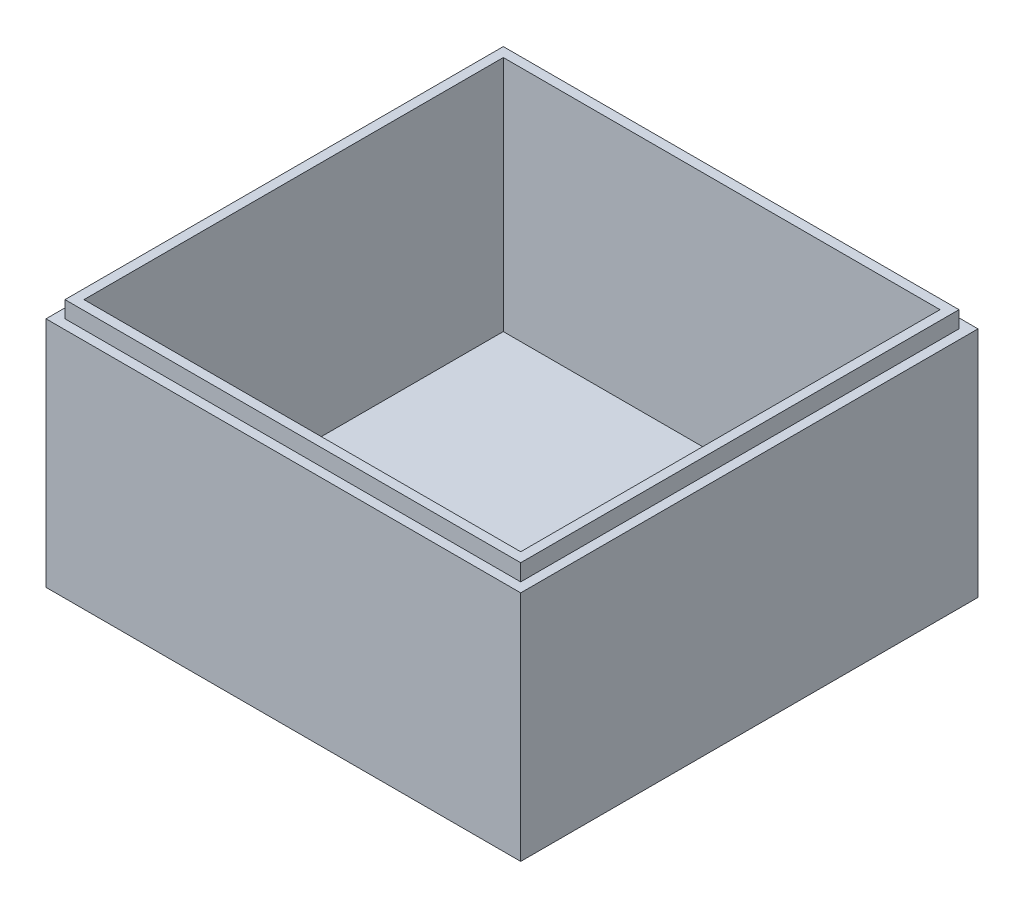
SolidWorks part; units mm, degrees
ref_plane "Front Plane" through (0, 0, 0) normal (0, 0, 1) x (1, 0, 0)
ref_plane "Top Plane" through (0, 0, 0) normal (0, 1, 0) x (1, 0, 0)
ref_plane "Right Plane" through (0, 0, 0) normal (1, 0, 0) x (0, 0, -1)
sketch "BatteryAndOuterWalls" plane through (0, 0, 0) normal (0, 1, 0) x (1, 0, 0)
  line L0 (30, -28.9) -> (30, 28.9)
  line L1 (27.6, -26.5) -> (-27.6, -26.5)
  line L2 (27.6, -26.5) -> (27.6, 26.5)
  line L3 (27.6, 26.5) -> (-27.6, 26.5)
  line L4 (-27.6, -26.5) -> (-27.6, 26.5)
  line L5 (27.6, -26.5) -> (-27.6, 26.5) construction
  line L6 (27.6, 26.5) -> (-27.6, -26.5) construction
  line L7 (30, 28.9) -> (-30, 28.9)
  line L8 (-30, -28.9) -> (-30, 28.9)
  line L9 (30, -28.9) -> (-30, -28.9)
  point P0 (0, 0)
  dimension "D1" = 55.2
  dimension "D2" = 53
  dimension "D4" = 60
  dimension "D5" = 57.8
  dimension "D3" = 2.4
extrude "Walls" add sketch "BatteryAndOuterWalls" along normal blind 30
sketch "SinkRim" plane through (0, 30, 0) normal (0, 1, 0) x (1, 0, 0)
  line L0 (-28.8, 27.7) -> (-28.8, -27.7)
  line L5 (-27.6, 26.5) -> (27.6, 26.5)
  line L6 (-27.6, 26.5) -> (-27.6, -26.5)
  line L7 (-27.6, -26.5) -> (27.6, -26.5)
  line L8 (27.6, 26.5) -> (27.6, -26.5)
  line L9 (-28.8, -27.7) -> (28.8, -27.7)
  line L10 (28.8, 27.7) -> (28.8, -27.7)
  line L11 (-28.8, 27.7) -> (28.8, 27.7)
  line L12 (-30, 28.9) -> (30, 28.9)
  line L13 (30, 28.9) -> (30, -28.9)
  line L14 (-30, -28.9) -> (30, -28.9)
  line L15 (-30, 28.9) -> (-30, -28.9)
  line M5 (-30, -28.9) -> (30, -28.9)
  line M6 (30, -28.9) -> (30, 28.9)
  line M7 (30, 28.9) -> (-30, 28.9)
  line M8 (-30, 28.9) -> (-30, -28.9)
  dimension "D1" = 1.2
  dimension "D2" = 1.2
sketch "Sketch2" plane through (0, 0, 0) normal (0, -1, 0) x (1, 0, 0)
  line L0 (-30, 28.9) -> (30, 28.9) construction
  line L5 (-30, 28.9) -> (30, 28.9)
  line L6 (-30, 28.9) -> (-30, -28.9)
  line L7 (-30, -28.9) -> (30, -28.9)
  line L8 (30, 28.9) -> (30, -28.9)
  line L9 (-30, -28.9) -> (-30, 28.9) construction
extrude "Bottom" add sketch "Sketch2" along normal blind 1.5
extrude "Top-Cut" cut sketch "SinkRim" against normal blind 2.1 contours L0 L11 L10 L9 M8 M5 M6 M7 region at (0, 30, -28.0669)
sketch "FrontRail" plane through (30, 0, 0) normal (1, 0, 0) x (0, 0, -1)
  line L0 (-28.9, 27.9) -> (-28.9, -1.5) construction
  line L1 (-26.5, 30) -> (26.5, 30)
  line L2 (-26.5, 30) -> (-26.5, 0)
  line L3 (-26.5, 0) -> (26.5, 0)
  line L4 (26.5, 30) -> (26.5, 0)
  line L5 (28.9, -1.5) -> (-28.9, -1.5) construction
  line L6 (28.9, 27.9) -> (28.9, -1.5) construction
  line L7 (27.7, 30) -> (-27.7, 30) construction
  line L8 (-26.5, 13) -> (-26.5, 14)
  line L10 (-26.5, 15) -> (-26.5, 14)
  line L29 (-26.5, 13) -> (-26.5, 14)
  line L30 (-26.5, 14) -> (-26.5, 13)
  line L32 (-26.5, 16.5) -> (26.5, 16.5)
  line L33 (-26.5, 16.5) -> (-26.5, 15)
  line L34 (-26.5, 15) -> (26.5, 15)
  line L35 (26.5, 16.5) -> (26.5, 15)
  line L36 (-22.5, 16.5) -> (22.5, 16.5)
  line L37 (-22.5, 16.5) -> (-22.5, 15)
  line L38 (-22.5, 15) -> (22.5, 15)
  line L41 (-22.5, 15) -> (-26.5, 15)
  line L42 (-22.5, 15) -> (-22.5, 14.95)
  line L43 (-23.45, 14) -> (-26.5, 14)
  line L44 (-26.5, 15) -> (-26.5, 14)
  arc A0 (-22.5, 14.95) -> (-23.45, 14) centre (-23.45, 14.95) cw
  point P26 (0, 0)
  point P27 (0, 0)
  point P28 (0, 0)
  point P29 (0, 0)
  dimension "D10" = 0.95
  dimension "D6" = 1.5
  dimension "D1" = 2.4
  dimension "D2" = 1.5
  dimension "D3" = 2.4
  dimension "D4" = 0
  dimension "D5" = 15
  dimension "D8" = 4
  dimension "D9" = 1
